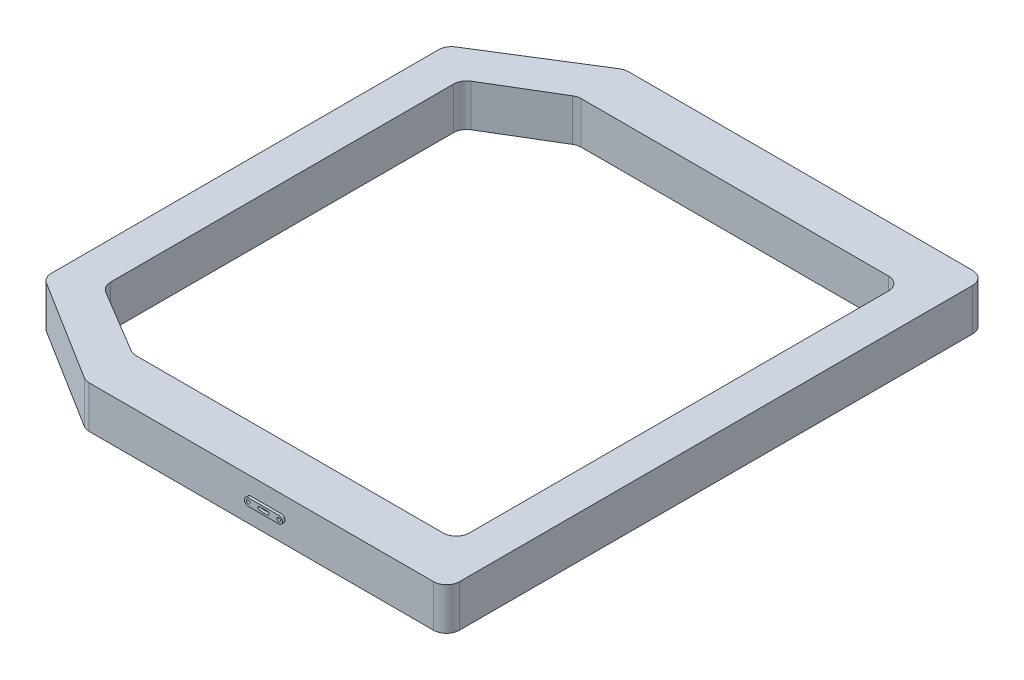
SolidWorks part; units mm, degrees
ref_plane "Alzado" through (0, 0, 0) normal (0, 0, 1) x (1, 0, 0)
ref_plane "Planta" through (0, 0, 0) normal (0, 1, 0) x (1, 0, 0)
ref_plane "Vista lateral" through (0, 0, 0) normal (1, 0, 0) x (0, 0, -1)
sketch "Croquis2" plane through (0, 0, 0) normal (0, 1, 0) x (1, 0, 0)
  line L2 (409.3806, 498.2225) -> (409.3806, -30.415)
  line L4 (55.3681, 15.6225) -> (372.8681, 15.6225)
  line L5 (-16.0694, 58.485) -> (-16.0694, 409.3225)
  line L8 (-16.0694, 409.3225) -> (55.3681, 452.185)
  line L11 (372.8681, 452.185) -> (55.3681, 452.185)
  line L16 (-16.0694, 58.485) -> (55.3681, 15.6225)
  line L17 (372.8681, 452.185) -> (372.8681, 15.6225)
  line L18 (409.3806, 498.2225) -> (55.3681, 498.2225)
  line L19 (-52.5819, 430.7538) -> (55.3681, 498.2225)
  line L21 (-52.5819, 37.0538) -> (55.3681, -30.415)
  line L22 (409.3806, -30.415) -> (55.3681, -30.415)
  line L23 (-52.5819, 37.0538) -> (-52.5819, 430.7538)
extrude "Saliente-Extruir2" add sketch "Croquis2" along normal blind 41.275 contours L19 L18 L2 L22 L21 L23
extrude "Cortar-Extruir2" cut sketch "Croquis2<5>" along normal blind 41.275 flip side to cut
sketch "Croquis2<5>" plane through (0, 0, 0) normal (0, 1, 0) x (1, 0, 0) same geometry as "Croquis2"
sketch "Croquis3" plane through (0, 0, 30.415) normal (0, 0, 1) x (1, 0, 0)
  line L2 (217.3863, 20.6375) -> (247.3625, 20.6375) construction
  line L3 (217.3863, 24.3066) -> (247.3625, 24.3066)
  line L4 (217.3863, 16.9684) -> (247.3625, 16.9684)
  line L5 (228.4334, 20.6375) -> (236.3154, 20.6375) construction
  line L6 (228.4334, 22.1951) -> (236.3154, 22.1951)
  line L7 (228.4334, 19.0799) -> (236.3154, 19.0799)
  arc A0 (217.3863, 24.3066) -> (217.3863, 16.9684) centre (217.3863, 20.6375) ccw
  arc A1 (247.3625, 16.9684) -> (247.3625, 24.3066) centre (247.3625, 20.6375) ccw
  circle A2 centre (217.3863, 20.6375) radius 1.7357
  circle A3 centre (247.3625, 20.6375) radius 1.7357
  arc A4 (228.4334, 22.1951) -> (228.4334, 19.0799) centre (228.4334, 20.6375) ccw
  arc A5 (236.3154, 19.0799) -> (236.3154, 22.1951) centre (236.3154, 20.6375) ccw
  point P0 (0, 0)
  point P10 (232.3744, 20.6375)
  point P21 (232.3744, 20.6375)
extrude "Saliente-Extruir4" add sketch "Croquis3" along normal blind 2.54 contours L4 A1 L3 A0
extrude "Cortar-Extruir3" cut sketch "Croquis3<5>" along normal blind 2.54 flip side to cut
sketch "Croquis3<5>" plane through (0, 0, 30.415) normal (0, 0, 1) x (1, 0, 0) same geometry as "Croquis3"
fillet "Redondeo1" radius 12.7 1 edges at (372.8681, 20.6375, -452.185) type face fillet first side face at (214.1181, 20.6375, -452.185) second side face at (372.8681, 20.6375, -233.9038)
fillet "Redondeo2" radius 12.7 1 edges at (372.8681, 20.6375, -15.6225) type face fillet first side face at (372.8681, 20.6375, -227.5538) second side face at (214.1181, 20.6375, -15.6225)
fillet "Redondeo3" radius 12.7 1 edges at (-16.0694, 20.6375, -409.3225) type face fillet first side face at (-16.0694, 20.6375, -233.9038) second side face at (19.6494, 20.6375, -430.7538)
fillet "Redondeo4" radius 12.7 1 edges at (55.3681, 20.6375, -452.185) type face fillet first side face at (22.7323, 20.6375, -432.6035) second side face at (207.7681, 20.6375, -452.185)
fillet "Redondeo5" radius 12.7 1 edges at (55.3681, 20.6375, -15.6225) type face fillet first side face at (207.7681, 20.6375, -15.6225) second side face at (19.6494, 20.6375, -37.0538)
fillet "Redondeo6" radius 12.7 1 edges at (-16.0694, 20.6375, -58.485) type face fillet first side face at (18.1412, 20.6375, -37.9587) second side face at (-16.0694, 20.6375, -230.3084)
fillet "Redondeo7" radius 12.7 1 edges at (55.3681, 20.6375, 30.415) type face fillet first side face at (232.3744, 20.6375, 30.415) second side face at (1.3931, 20.6375, -3.3194)
fillet "Redondeo8" radius 12.7 1 edges at (-52.5819, 20.6375, -37.0538) type face fillet first side face at (-0.1512, 20.6375, -4.2846) second side face at (-52.5819, 20.6375, -233.9038)
fillet "Redondeo9" radius 12.7 1 edges at (-52.5819, 20.6375, -430.7538) type face fillet first side face at (-52.5819, 20.6375, -237.4232) second side face at (1.3931, 20.6375, -464.4881)
fillet "Redondeo10" radius 12.7 1 edges at (55.3681, 20.6375, -498.2225) type face fillet first side face at (4.3777, 20.6375, -466.3534) second side face at (232.3744, 20.6375, -498.2225)
fillet "Redondeo11" radius 12.7 1 edges at (409.3806, 20.6375, 30.415) type face fillet first side face at (234.1956, 20.6375, 30.415) second side face at (409.3806, 20.6375, -233.9038)
fillet "Redondeo12" radius 12.7 1 edges at (409.3806, 20.6375, -498.2225) type face fillet first side face at (234.1956, 20.6375, -498.2225) second side face at (409.3806, 20.6375, -240.2538)
